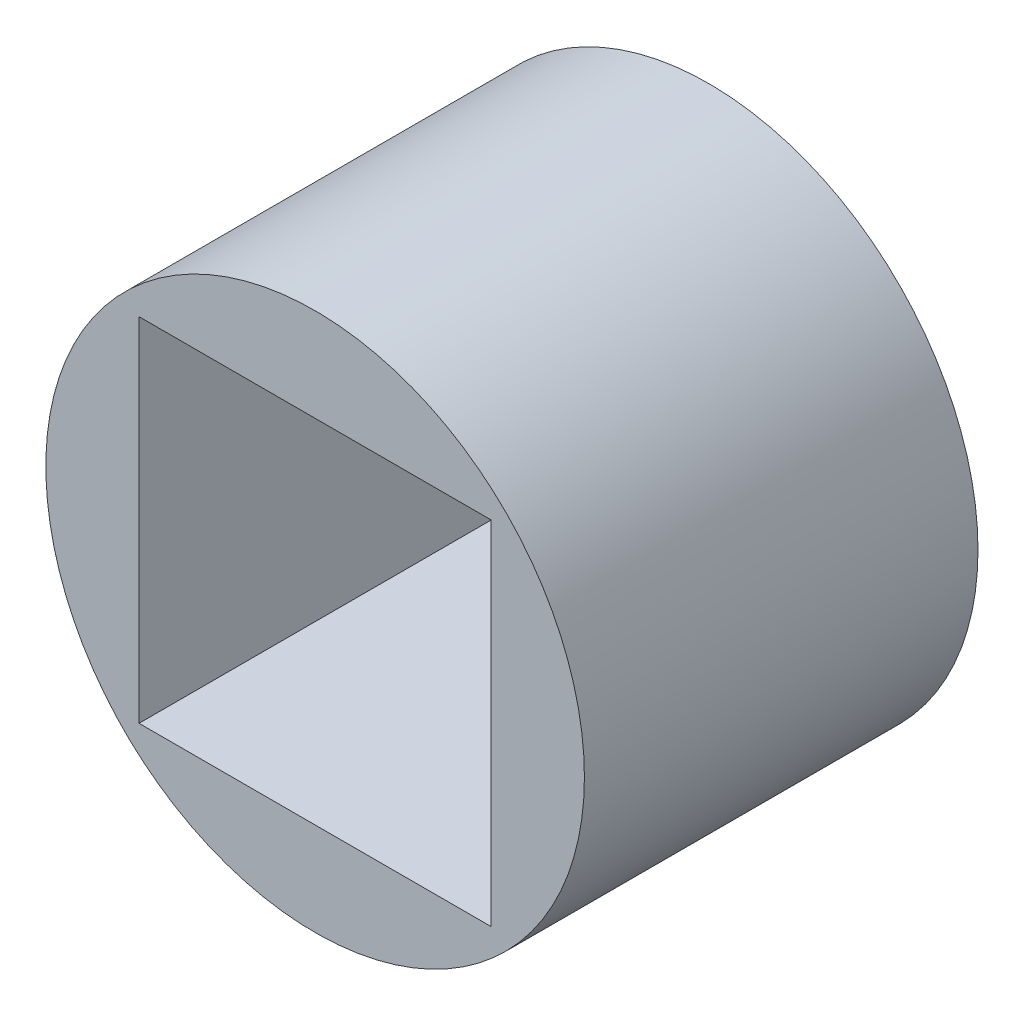
SolidWorks part; units mm, degrees
ref_plane "Front Plane" through (0, 0, 0) normal (0, 0, 1) x (1, 0, 0)
ref_plane "Top Plane" through (0, 0, 0) normal (0, 1, 0) x (1, 0, 0)
ref_plane "Right Plane" through (0, 0, 0) normal (1, 0, 0) x (0, 0, -1)
sketch "Sketch1" plane through (0, 0, 0) normal (0, 0, 1) x (1, 0, 0)
  circle A0 centre (0, 0) radius 13.25 construction
  circle A1 centre (0, 0) radius 13.25 construction
  circle A2 centre (0, 0) radius 13
  dimension "D1" = 26.5
  dimension "D2" = 0
  dimension "D3" = 0.25
extrude "Boss-Extrude1" add sketch "Sketch1" along normal blind 19
sketch "Sketch2" plane through (0, 0, 0) normal (0, 0, -1) x (-1, 0, 0)
  line L1 (-8.5, -8.5) -> (8.5, -8.5)
  line L2 (-8.5, -8.5) -> (-8.5, 8.5)
  line L3 (-8.5, 8.5) -> (8.5, 8.5)
  line L4 (8.5, -8.5) -> (8.5, 8.5)
  line L5 (-8.5, -8.5) -> (8.5, 8.5) construction
  line L6 (-8.5, 8.5) -> (8.5, -8.5) construction
  point P0 (0, 0)
  dimension "D1" = 17
  dimension "D2" = 17
extrude "Cut-Extrude1" cut sketch "Sketch2" against normal through all
sketch "Sketch3" plane through (0, 8.5, 0) normal (0, -1, 0) x (1, 0, 0)
  line L0 (-8.5018, 7.4231) -> (8.1138, 7.4231) construction
  text T0 "CSS-1" font "@Adobe Fan Heiti Std B" height in points 12
extrude "Cut-Extrude2" cut sketch "Sketch3" against normal blind 1
